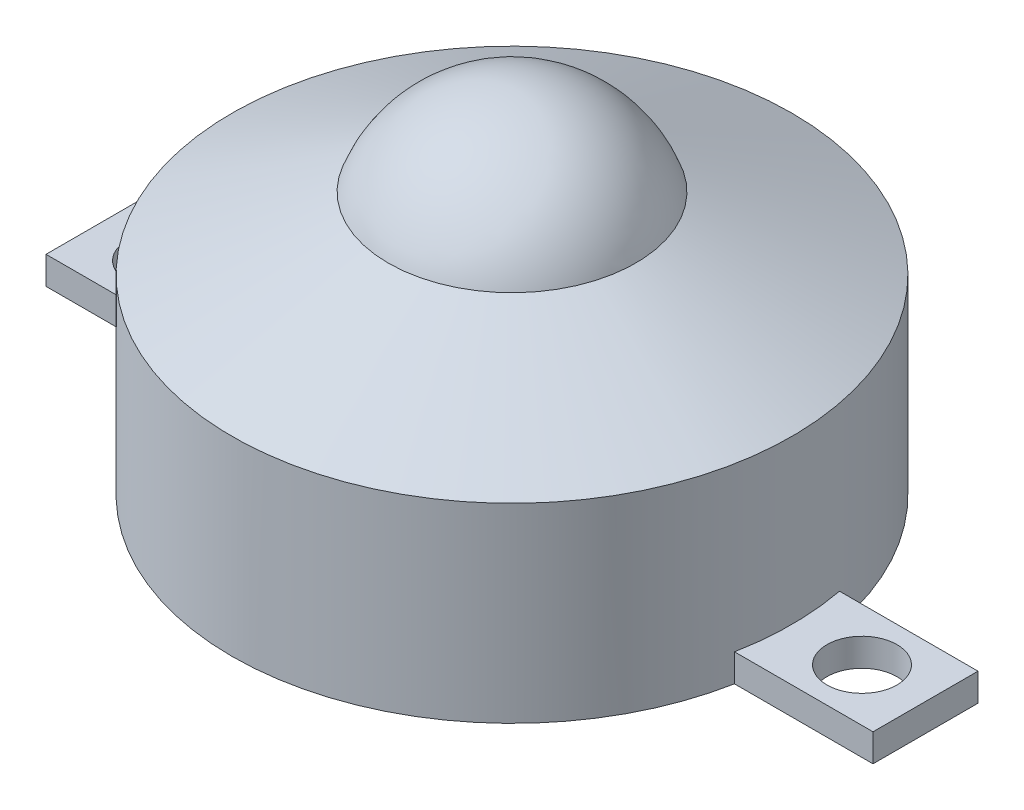
SolidWorks part; units mm, degrees
ref_plane "Front Plane" through (0, 0, 0) normal (0, 0, 1) x (1, 0, 0)
ref_plane "Top Plane" through (0, 0, 0) normal (0, 1, 0) x (1, 0, 0)
ref_plane "Right Plane" through (0, 0, 0) normal (1, 0, 0) x (0, 0, -1)
sketch "Sketch1" plane through (0, 0, 0) normal (0, 0, 1) x (1, 0, 0)
  line L1 (0, 0) -> (16, 0)
  line L2 (16, 0) -> (16, 10.8913)
  line L3 (16, 10.8913) -> (7.07, 15)
  line L4 (0, 0) -> (0, 20)
  line L5 (0, 20) -> (0, 15)
  arc A1 (0, 20) -> (7.07, 15) centre (0, 12.5015) cw
  dimension "D1" = 20
  dimension "D2" = 7.07
  dimension "D4" = 16
revolve "Revolve2" add sketch "Sketch1" angle 360 about L4 region at (7.0887, 8.0426, 0)
sketch "Sketch5" plane through (0, 0, 0) normal (0, -1, 0) x (1, 0, 0)
  line L5 (23.6308, 0) -> (23.6308, 3)
  line L6 (23.6308, 3) -> (15.7162, 3)
  line L7 (23.6308, 0) -> (23.6308, -3)
  line L8 (23.6308, -3) -> (15.7162, -3)
  line L9 (-23.6308, 0) -> (-23.6308, 3)
  line L10 (-23.6308, 0) -> (-23.6308, -3)
  line L11 (-23.6308, 3) -> (-15.7162, 3)
  line L12 (-23.6308, -3) -> (-15.7162, -3)
  circle A0 centre (0, 0) radius 16 construction
  circle A1 centre (-20, 0) radius 2
  circle A2 centre (20, 0) radius 2
  arc A3 (-15.7162, 3) -> (15.7162, 3) centre (0, 0) cw
  arc A4 (-15.7162, -3) -> (15.7162, -3) centre (0, 0) ccw
  dimension "D1" = 4
  dimension "D2" = 4
  dimension "D3" = 40
  dimension "D4" = 0
  dimension "D5" = 0
  dimension "D6" = 20
  dimension "D7" = 3
  dimension "D8" = 3
  dimension "D9" = 3.6308
  dimension "D10" = 3.6308
  dimension "D11" = 3
  dimension "D12" = 3
extrude "Boss-Extrude1" add sketch "Sketch5" against normal blind 1.5875
